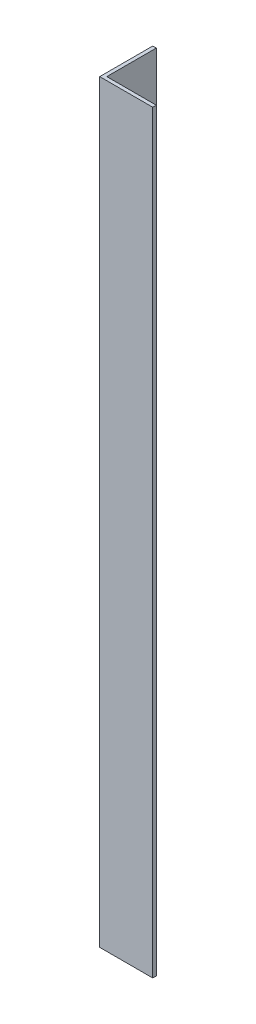
SolidWorks part; units mm, degrees
ref_plane "Спереди" through (0, 0, 0) normal (0, 0, 1) x (1, 0, 0)
ref_plane "Сверху" through (0, 0, 0) normal (0, 1, 0) x (1, 0, 0)
ref_plane "Справа" through (0, 0, 0) normal (1, 0, 0) x (0, 0, -1)
sketch "Эскиз1" plane through (0, 0, 0) normal (0, 1, 0) x (1, 0, 0)
  line L0 (0, 45) -> (0, 0)
  line L1 (0, 0) -> (45, 0)
extrude "Вытянуть-Тонкостенный1" add sketch "Эскиз1" along normal blind 640 thin thin type one direction reverse wall 3
